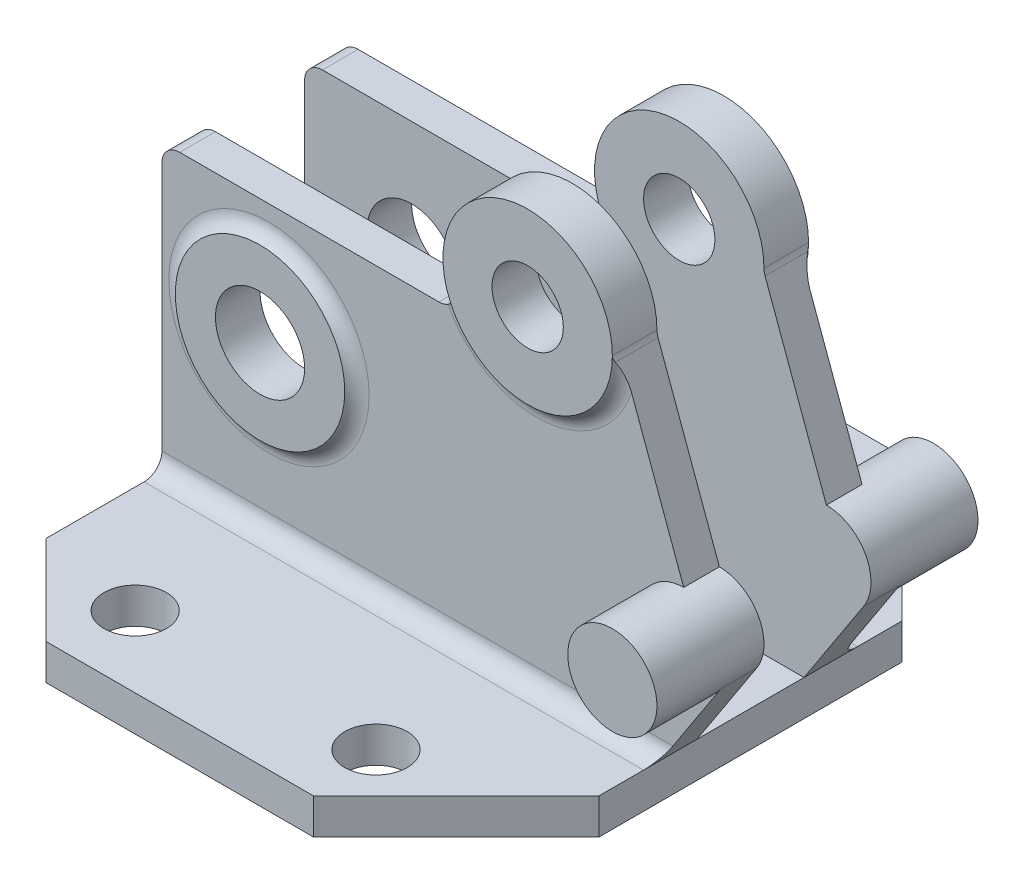
SolidWorks part; units mm, degrees
material "Cast Carbon Steel"
ref_plane "Front Plane" through (0, 0, 0) normal (0, 0, 1) x (1, 0, 0)
ref_plane "Top Plane" through (0, 0, 0) normal (0, 1, 0) x (1, 0, 0)
ref_plane "Right Plane" through (0, 0, 0) normal (1, 0, 0) x (0, 0, -1)
sketch "Sketch1" plane through (0, 0, 0) normal (0, 1, 0) x (1, 0, 0)
  line L8 (0, -12.1937) -> (0, -58.1937)
  line L9 (0, -58.1937) -> (10, -68.1937)
  line L10 (10, -68.1937) -> (40, -68.1937)
  line L11 (40, -68.1937) -> (56, -52.1937)
  line L12 (56, -52.1937) -> (56, -18.1937)
  line L13 (56, -18.1937) -> (40, -2.1937)
  line L14 (40, -2.1937) -> (10, -2.1937)
  line L15 (10, -2.1937) -> (0, -12.1937)
  line L16 (10, -2.1937) -> (-69.487, -2.1937) construction
  line L17 (10, -68.1937) -> (-78.2018, -68.1937) construction
  line L18 (40, -68.1937) -> (146.4707, -68.1937) construction
  line L19 (40, -2.1937) -> (143.2263, -2.1937) construction
  line L20 (25.5, 10.7474) -> (25.5, -110.5321) construction
  line L21 (-2.9445, -35.1937) -> (92.5262, -35.1937) construction
  circle A0 centre (12, -10.1937) radius 3.5
  circle A1 centre (12, -60.1937) radius 3.5
  circle A2 centre (39, -60.1937) radius 3.5
  circle A3 centre (39, -10.1937) radius 3.5
  dimension "D12" = 7
  dimension "D1" = 45
  dimension "D2" = 45
  dimension "D3" = 45
  dimension "D4" = 10
  dimension "D5" = 16
  dimension "D6" = 16
  dimension "D7" = 10
  dimension "D8" = 66
  dimension "D9" = 56
  dimension "D10" = 12
  dimension "D11" = 8
  dimension "D13" = 13.5
extrude "Boss-Extrude1" add sketch "Sketch1" along normal blind 4
ref_plane "Plane1" through (0, 0, 45.1937) normal (0, 0, 1) x (1, 0, 0)
sketch "Sketch3" plane through (0, 0, 45.1937) normal (0, 0, 1) x (1, 0, 0)
  line L0 (0, 4) -> (0, 36)
  line L1 (10, 4) -> (40, 4) construction
  line L2 (0, 36) -> (31.0554, 36)
  line L3 (62.6977, 14.2684) -> (56, 4)
  line L4 (58.5098, 22) -> (51.6314, 40.8132)
  line L5 (0, 4) -> (10, 4) construction
  line L7 (0, 4) -> (0, 0) construction
  line L8 (40, 4) -> (56, 4) construction
  line L9 (0, 4) -> (56, 4)
  arc A0 (31.0554, 36) -> (32.9605, 38.6087) centre (31.0554, 38) ccw
  circle A1 centre (42.0098, 41.5) radius 9.5
  circle A2 centre (58.5098, 17) radius 5
  arc A3 (51.6314, 40.8132) -> (51.5098, 41.5) centre (53.5098, 41.5) cw
  circle A4 centre (12, 23) radius 5
  circle A5 centre (12, 23) radius 9.5
  circle A6 centre (42.0098, 41.5) radius 4
  dimension "D3" = 19
  dimension "D4" = 10
  dimension "D7" = 19
  dimension "D8" = 8
  dimension "D11" = 10
  dimension "D12" = 2
  dimension "D1" = 32
  dimension "D2" = 19
  dimension "D5" = 12
  dimension "D6" = 37.5
  dimension "D9" = 16.5
  dimension "D10" = 13
extrude "Boss-Extrude2" add sketch "Sketch3" against normal blind 4 contours L4 A3 A1 A0 L2 L0 L9 L3 A2 A5 | A2 | A5 A4 | A1 A6 region at (30.9686, 18.935, 45.1937) region at (58.5098, 17, 45.1937) region at (40.5881, 50.6212, 45.1937) region at (2.7687, 23, 45.1937)
extrude "Boss-Extrude3" add sketch "Sketch3<3>" along normal blind 1 contours A5 A4 | A1 A6 region at (40.5881, 50.6212, 45.1937) region at (2.7687, 23, 45.1937)
sketch "Sketch3<3>" plane through (0, 0, 45.1937) normal (0, 0, 1) x (1, 0, 0) same geometry as "Sketch3"
extrude "Boss-Extrude4" add sketch "Sketch3<4>" along normal blind 8 contours A2 region at (58.5098, 17, 45.1937)
sketch "Sketch3<4>" plane through (0, 0, 45.1937) normal (0, 0, 1) x (1, 0, 0) same geometry as "Sketch3"
ref_plane "Plane2" through (0, 0, 35.1937) normal (0, 0, -1) x (-1, 0, 0)
mirror "Mirror1" about plane through (0, 0, 35.1937) normal (0, 0, -1) of "Boss-Extrude4", "Boss-Extrude3", "Boss-Extrude2"
fillet "Fillet1" radius 2 8 edges at (0, 36, 43.1937) (0, 36, 27.1937) (43.4729, 32.1133, 25.1937) (2.5, 23, 25.1937) (28, 4, 25.1937) (28, 4, 45.1937) (43.4729, 32.1133, 45.1937) (21.5, 23, 45.1937)
